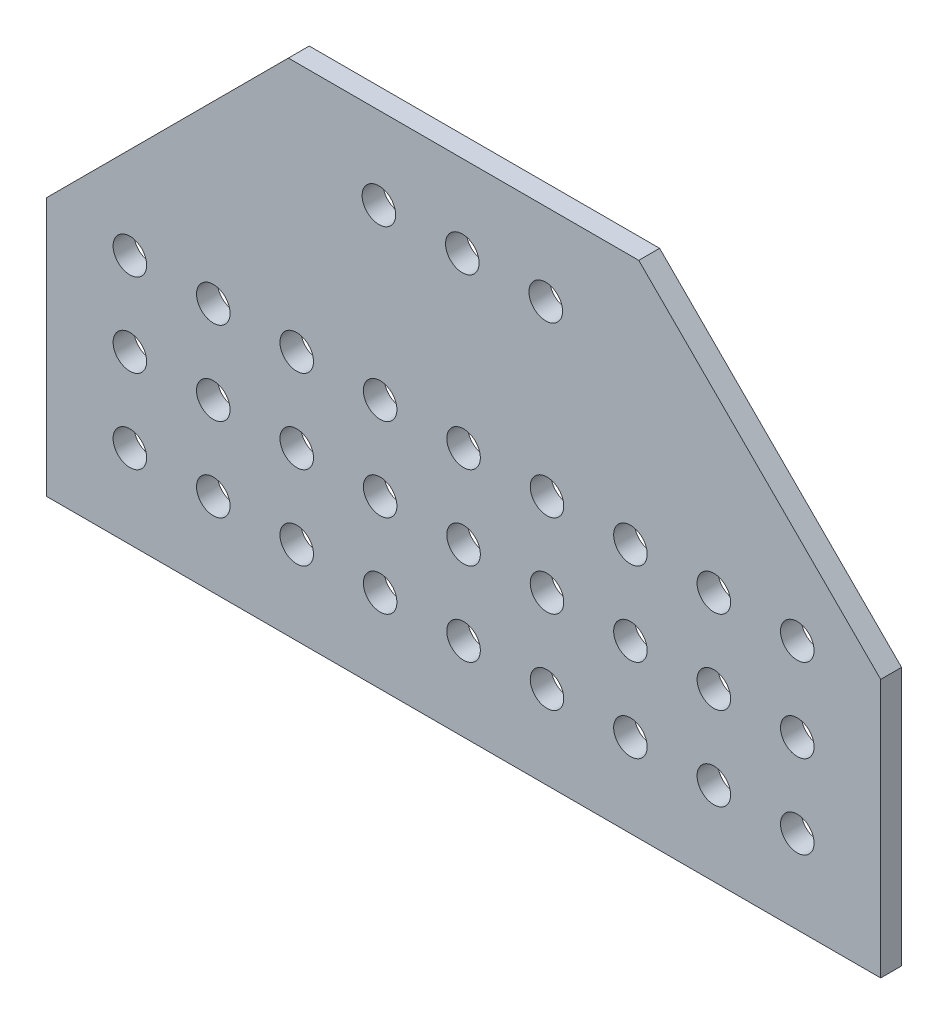
SolidWorks part; units mm, degrees
material "6061-T6 (SS)"
ref_plane "Front Plane" through (0, 0, 0) normal (0, 0, 1) x (1, 0, 0)
ref_plane "Top Plane" through (0, 0, 0) normal (0, 1, 0) x (1, 0, 0)
ref_plane "Right Plane" through (0, 0, 0) normal (1, 0, 0) x (0, 0, -1)
sketch "Sketch1" plane through (0, 0, 0) normal (0, 0, 1) x (1, 0, 0)
  line L1 (0, 0) -> (127, 0)
  line L2 (0, 0) -> (0, 82.55)
  line L3 (0, 82.55) -> (127, 82.55)
  line L4 (127, 0) -> (127, 82.55)
  dimension "D1" = 82.55
  dimension "D2" = 127
extrude "Boss-Extrude1" add sketch "Sketch1" along normal blind 3.175
sketch "Sketch2" plane through (0, 0, 0) normal (0, 0, -1) x (-1, 0, 0)
  line L0 (-127, 82.55) -> (0, 82.55) construction
  line L1 (0, 82.55) -> (0, 0) construction
  circle A0 centre (-76.0095, 63.6905) radius 2.5527
  circle A1 centre (-63.3095, 63.6905) radius 2.5527
  circle A2 centre (-50.6095, 63.6905) radius 2.5527
  point P9 (0, 0)
  point P10 (0, 0)
  dimension "D1" = 18.8595
  dimension "D2" = 12.7
  dimension "D3" = 12.7
  dimension "D4" = 50.6095
  dimension "D5" = 18.8595
  dimension "D6" = 18.8595
  dimension "D7" = 5.1054
  dimension "D8" = 5.1054
  dimension "D9" = 5.1054
extrude "Cut-Extrude1" cut sketch "Sketch2" against normal through all and the other way through all
sketch "Sketch3" plane through (0, 0, 0) normal (0, 0, -1) x (-1, 0, 0)
  line L0 (-127, 0) -> (-127, 82.55) construction
  line L1 (0, 0) -> (-127, 0) construction
  circle A0 centre (-114.3, 38.1) radius 2.5527
  circle A1 centre (-114.3, 25.4) radius 2.5527
  circle A2 centre (-114.3, 12.7) radius 2.5527
  circle A3 centre (-101.6, 38.1) radius 2.5527
  circle A4 centre (-101.6, 25.4) radius 2.5527
  circle A5 centre (-101.6, 12.7) radius 2.5527
  circle A6 centre (-88.9, 38.1) radius 2.5527
  circle A7 centre (-88.9, 25.4) radius 2.5527
  circle A8 centre (-88.9, 12.7) radius 2.5527
  circle A9 centre (-76.2, 38.1) radius 2.5527
  circle A10 centre (-76.2, 25.4) radius 2.5527
  circle A11 centre (-76.2, 12.7) radius 2.5527
  circle A12 centre (-63.5, 38.1) radius 2.5527
  circle A13 centre (-63.5, 25.4) radius 2.5527
  circle A14 centre (-63.5, 12.7) radius 2.5527
  circle A15 centre (-50.8, 38.1) radius 2.5527
  circle A16 centre (-50.8, 25.4) radius 2.5527
  circle A17 centre (-50.8, 12.7) radius 2.5527
  circle A18 centre (-38.1, 38.1) radius 2.5527
  circle A19 centre (-38.1, 25.4) radius 2.5527
  circle A20 centre (-38.1, 12.7) radius 2.5527
  circle A21 centre (-25.4, 38.1) radius 2.5527
  circle A22 centre (-25.4, 25.4) radius 2.5527
  circle A23 centre (-25.4, 12.7) radius 2.5527
  circle A24 centre (-12.7, 38.1) radius 2.5527
  circle A25 centre (-12.7, 25.4) radius 2.5527
  circle A26 centre (-12.7, 12.7) radius 2.5527
  dimension "D1" = 5.1054
  dimension "D2" = 5.1054
  dimension "D3" = 5.1054
  dimension "D4" = 12.7
  dimension "D5" = 12.7
  dimension "D6" = 12.7
  dimension "D7" = 12.7
  dimension "D8" = 12.7
  dimension "D9" = 12.7
  dimension "D11" = 12.7
  dimension "D10" = 9
extrude "Cut-Extrude2" cut sketch "Sketch3" against normal through all
sketch "Sketch4" plane through (0, 0, 0) normal (0, 0, -1) x (-1, 0, 0)
  line L0 (-83.82, 82.55) -> (-127, 39.37)
  line L1 (-127, 82.55) -> (0, 82.55) construction
  line L2 (-127, 39.37) -> (-127, 82.55)
  line L3 (-127, 82.55) -> (-83.82, 82.55)
  line L4 (-43.18, 82.55) -> (0, 82.55)
  line L5 (0, 82.55) -> (0, 39.37)
  line L6 (0, 82.55) -> (0, 0) construction
  line L7 (0, 39.37) -> (-43.18, 82.55)
  dimension "D1" = 45
  dimension "D2" = 45
  dimension "D3" = 43.18
  dimension "D4" = 43.18
extrude "Cut-Extrude3" cut sketch "Sketch4" against normal through all
sketch "Sketch5" plane through (0, 0, 0) normal (0, 0, -1) x (-1, 0, 0)
  line L0 (-90.17, 76.2) -> (-36.83, 76.2)
  line L1 (-127, 39.37) -> (-83.82, 82.55) construction
  line L2 (-43.18, 82.55) -> (0, 39.37) construction
  line L3 (-36.83, 76.2) -> (-43.18, 82.55)
  line L4 (-43.18, 82.55) -> (-83.82, 82.55)
  line L5 (-83.82, 82.55) -> (-90.17, 76.2)
  dimension "D1" = 6.35
extrude "Cut-Extrude4" cut sketch "Sketch5" against normal through all
